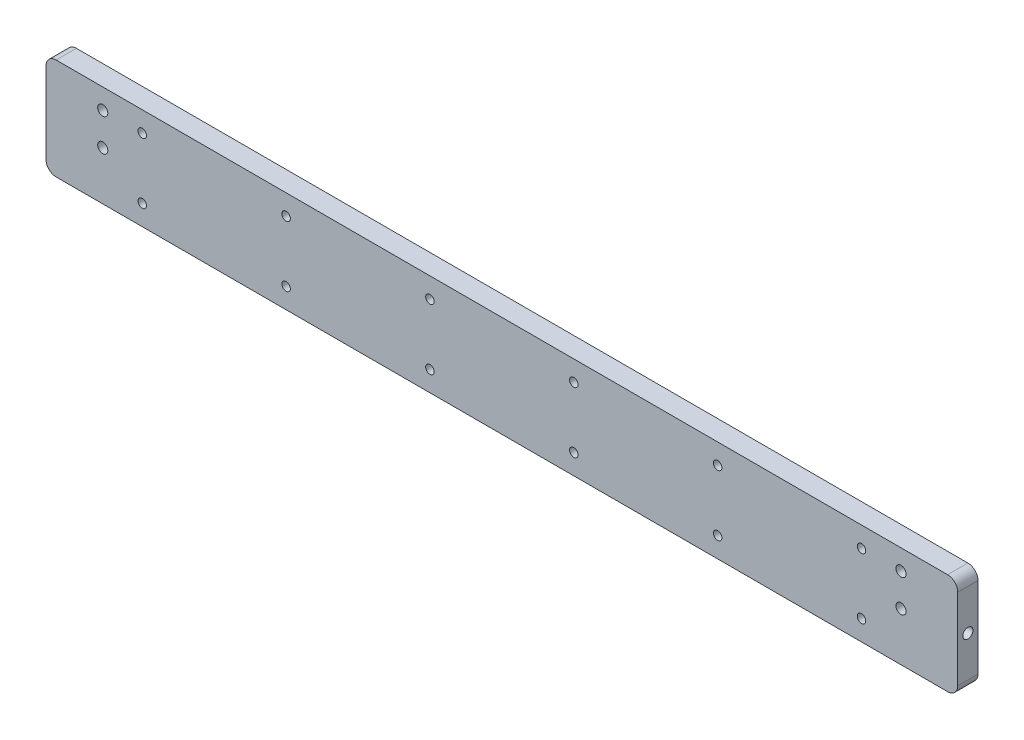
SolidWorks part; units mm, degrees
ref_plane "Front" through (0, 0, 0) normal (0, 0, 1) x (1, 0, 0)
ref_plane "Top" through (0, 0, 0) normal (0, 1, 0) x (1, 0, 0)
ref_plane "Right" through (0, 0, 0) normal (1, 0, 0) x (0, 0, -1)
sketch "Esquisse1" plane through (0, 0, 0) normal (0, 0, 1) x (1, 0, 0)
  line L1 (0, 0) -> (450, 0)
  line L2 (0, 0) -> (0, 50)
  line L3 (0, 50) -> (450, 50)
  line L4 (450, 0) -> (450, 50)
  dimension "D1" = 50
  dimension "D2" = 450
extrude "Boss.-Extru.1" add sketch "Esquisse1" along normal blind 10
sketch "Esquisse2" plane through (0, 0, 0) normal (-1, 0, 0) x (0, 0, 1)
  line L0 (5, 50) -> (5, 0) construction
  line L1 (10, 50) -> (0, 50) construction
  line L2 (10, 0) -> (0, 0) construction
  circle A0 centre (5, 25) radius 2.5
  dimension "D1" = 5
extrude "Enlèv. mat.-Extru.1" cut sketch "Esquisse2" against normal blind 16
extrude "Enlèv. mat.-Extru.2" cut sketch "Esquisse2<2>" along normal blind 20 from vertex starting at point (450, 50, 10)
sketch "Esquisse2<2>" plane through (0, 0, 0) normal (-1, 0, 0) x (0, 0, 1) same geometry as "Esquisse2"
fillet "Congé1" radius 5 4 edges at (0, 50, 5) (0, 0, 5) (450, 0, 5) (450, 50, 5)
sketch "Esquisse3" plane through (0, 0, 0) normal (0, 0, -1) x (-1, 0, 0)
  line L0 (-450, 25) -> (0, 25) construction
  line L1 (-450, 5) -> (-450, 45) construction
  line L2 (0, 45) -> (0, 5) construction
  line L3 (-225, 25) -> (-225, 50) construction
  line L4 (-445, 50) -> (-5, 50) construction
  line L5 (-296, 50) -> (-296, 0) construction
  line L6 (-5, 0) -> (-445, 0) construction
  line L7 (-367, 50) -> (-367, 0) construction
  line L8 (-83, 50) -> (-83, 0) construction
  line L9 (-154, 50) -> (-154, 0) construction
  circle A0 centre (-260.5, 40) radius 2.1
  circle A1 centre (-260.5, 10) radius 2.1
  circle A2 centre (-331.5, 10) radius 2.1
  circle A3 centre (-331.5, 40) radius 2.1
  circle A4 centre (-402.5, 40) radius 2.1
  circle A5 centre (-402.5, 10) radius 2.1
  circle A6 centre (-47.5, 10) radius 2.1
  circle A7 centre (-47.5, 40) radius 2.1
  circle A8 centre (-118.5, 40) radius 2.1
  circle A9 centre (-118.5, 10) radius 2.1
  circle A10 centre (-189.5, 10) radius 2.1
  circle A11 centre (-189.5, 40) radius 2.1
  dimension "D1" = 71
  dimension "D2" = 30
  dimension "D3" = 4.2
  dimension "D4" = 71
  dimension "D5" = 71
extrude "Enlèv. mat.-Extru.3" cut sketch "Esquisse3" against normal through all both and the other way through all
sketch "Esquisse4" plane through (0, 0, 10) normal (0, 0, 1) x (1, 0, 0)
  line L0 (0, 32) -> (28, 32) construction
  line L1 (0, 45) -> (0, 5) construction
  line L2 (28, 32) -> (28, 40) construction
  line L3 (5, 0) -> (445, 0) construction
  line L4 (225, 0) -> (225, 50) construction
  line L5 (445, 50) -> (5, 50) construction
  line L6 (422, 32) -> (422, 40) construction
  line L7 (450, 32) -> (422, 32) construction
  circle A0 centre (28, 40) radius 2.5
  circle A1 centre (28, 24) radius 2.5
  circle A2 centre (422, 24) radius 2.5
  circle A3 centre (422, 40) radius 2.5
  dimension "D1" = 5
  dimension "D2" = 16
  dimension "D3" = 28
  dimension "D4" = 18
extrude "Enlèv. mat.-Extru.4" cut sketch "Esquisse4" against normal through all both and the other way through all
